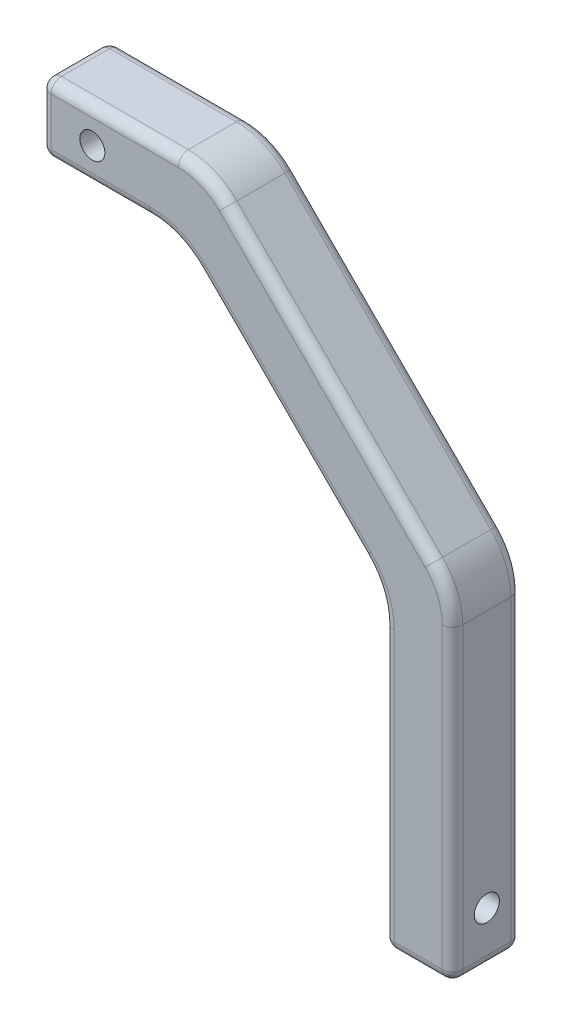
SolidWorks part; units mm, degrees
ref_plane "Alzado" through (0, 0, 0) normal (0, 0, 1) x (1, 0, 0)
ref_plane "Planta" through (0, 0, 0) normal (0, 1, 0) x (1, 0, 0)
ref_plane "Vista lateral" through (0, 0, 0) normal (1, 0, 0) x (0, 0, -1)
sketch "Croquis1" plane through (0, 0, 0) normal (0, 0, 1) x (1, 0, 0)
  line L0 (-60, 0) -> (60, 0) construction
  line L1 (-60, 0) -> (-11.7157, 0)
  line L2 (-11.7157, 0) -> (60, -71.7157)
  line L3 (60, -71.7157) -> (60, -170)
  line L4 (60, -170) -> (40, -170)
  line L5 (40, -170) -> (40, -80)
  line L6 (40, -80) -> (-20, -20)
  line L7 (-20, -20) -> (-60, -20)
  line L8 (-60, -20) -> (-60, 0)
  line L9 (60, -170) -> (60, -160) construction
  line L10 (-60, -10) -> (-45, -10) construction
  line L11 (50, -170) -> (50, -155) construction
  circle A0 centre (-45, -10) radius 3.65
  point P0 (-60, -10)
  point P4 (0, 0)
  dimension "D9" = 7.3
  dimension "D1" = 150
  dimension "D2" = 120
  dimension "D3" = 20
  dimension "D4" = 20
  dimension "D5" = 20
  dimension "D6" = 90
  dimension "D7" = 40
  dimension "D8" = 10
  dimension "D10" = 15
  dimension "D11" = 15
extrude "Saliente-Extruir1" add sketch "Croquis1" along normal blind 20 contours L1 L2 L3 L4 L5 L6 L7 L8 | A0
sketch "Croquis2" plane through (0, 0, 20) normal (0, 0, 1) x (1, 0, 0)
  line L0 (-60, -20) -> (-20, -20)
  line L1 (-20, -20) -> (-20, 0)
  line L2 (-60, 0) -> (-11.7157, 0) construction
  line L3 (-20, 0) -> (-60, 0)
  line L4 (-60, 0) -> (-60, -20)
extrude "Cortar-Extruir1" [suppressed] cut sketch "Croquis2" against normal blind 10
sketch "Croquis3" plane through (60, 0, 0) normal (1, 0, 0) x (0, 0, -1)
  line L0 (-20, -170) -> (0, -170)
  line L1 (0, -170) -> (0, -150)
  line L2 (0, -71.7157) -> (0, -170) construction
  line L3 (0, -150) -> (-20, -150)
  line L4 (-20, -71.7157) -> (-20, -170) construction
  line L5 (-20, -150) -> (-20, -170)
  dimension "D1" = 20
extrude "Cortar-Extruir2" [suppressed] cut sketch "Croquis3" against normal blind 10
fillet "Redondeo1" radius 20 4 edges at (40, -80, 10) (60, -71.7157, 10) (-20, -20, 10) (-11.7157, 0, 10)
sketch "Croquis4" plane through (40, 0, 0) normal (-1, 0, 0) x (0, 0, 1)
  line L0 (10, -170) -> (10, -155) construction
  line L1 (20, -170) -> (0, -170) construction
  circle A0 centre (10, -155) radius 3.65
  dimension "D2" = 7.3
  dimension "D1" = 15
extrude "Cortar-Extruir3" cut sketch "Croquis4" against normal blind 20
fillet "Redondeo2" radius 3 28 edges at (-40, 0, 20) (-12.3463, -1.5224, 20) (60, -125, 20) (58.4776, -72.3463, 20) (40, -129.1421, 20) (38.4776, -80.6306, 20) (-44.1421, -20, 20) (-20.6306, -21.5224, 20) (-40, 0, 0) (-12.3463, -1.5224, 0) (60, -125, 0) (58.4776, -72.3463, 0) (40, -129.1421, 0) (38.4776, -80.6306, 0) (-44.1421, -20, 0) (-20.6306, -21.5224, 0) (24.1421, -35.8579, 20) (10, -50, 20) (24.1421, -35.8579, 0) (10, -50, 0) (40, -170, 10) (50, -170, 0) (50, -170, 20) (60, -170, 10) (-60, -20, 10) (-60, -10, 0) (-60, -10, 20) (-60, 0, 10)
